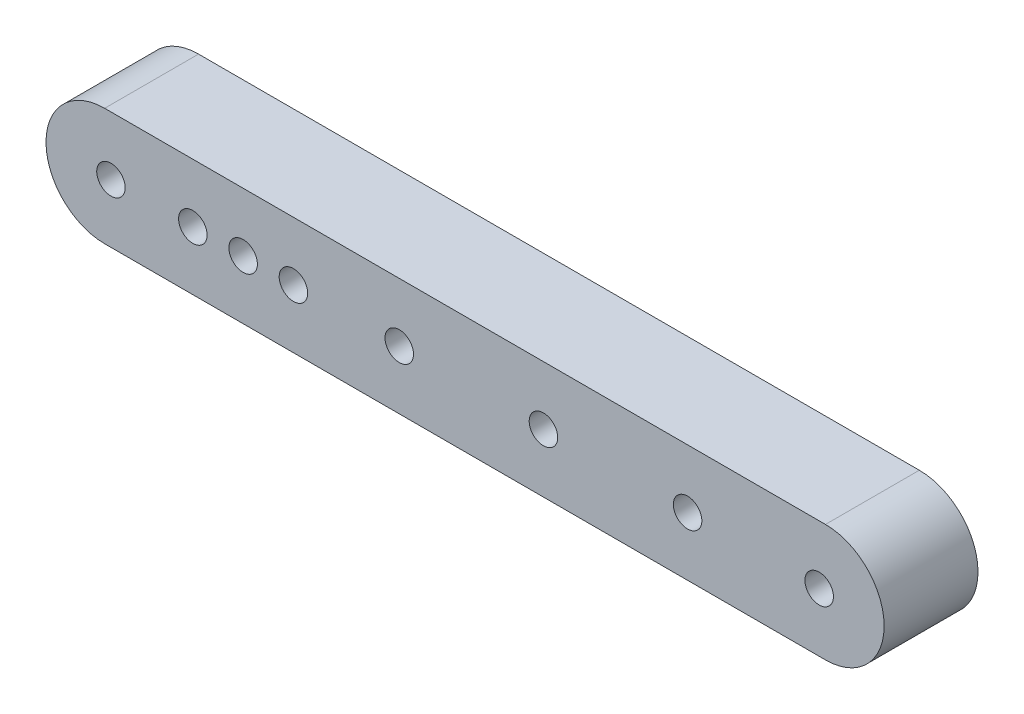
SolidWorks part; units mm, degrees
ref_plane "Front Plane" through (0, 0, 0) normal (0, 0, 1) x (1, 0, 0)
ref_plane "Top Plane" through (0, 0, 0) normal (0, 1, 0) x (1, 0, 0)
ref_plane "Right Plane" through (0, 0, 0) normal (1, 0, 0) x (0, 0, -1)
sketch "Sketch1" plane through (0, 0, 0) normal (0, 0, 1) x (1, 0, 0)
  line L0 (-33.3096, 0) -> (9.6904, 0) construction
  line L1 (-33.3096, 3.5) -> (9.6904, 3.5)
  line L2 (-33.3096, -3.5) -> (9.6904, -3.5)
  arc A0 (-33.3096, 3.5) -> (-33.3096, -3.5) centre (-33.3096, 0) ccw
  arc A1 (9.6904, -3.5) -> (9.6904, 3.5) centre (9.6904, 0) ccw
  point P3 (-11.8096, 0)
  point P8 (-36.8096, 0)
  point P9 (13.1904, 0)
  dimension "D1" = 50
  dimension "D2" = 7
extrude "Boss-Extrude1" add sketch "Sketch1" along normal blind 2.8 and the other way blind 2.8
scale "Echelle1" scale about centroid uniform scaling yes scale factor 2
sketch "Sketch2" plane through (0, 0, -5.6) normal (0, 0, 1) x (1, 0, 0)
  circle A3 centre (-38.2896, 0) radius 1.7
  circle A7 centre (-54.0596, 0) radius 1.7
  circle A29 centre (-19.6596, 0) radius 1.7
  circle A30 centre (-2.4596, 0) radius 1.7
  circle A31 centre (14.7404, 0) radius 1.7
  circle A33 centre (-44.2896, 0) radius 1.7
  circle A34 centre (-36.8596, 0) radius 1.7 [skipped]
  circle A35 centre (-32.2896, 0) radius 1.7
  arc A36 (-54.8096, 7) -> (-54.8096, -7) centre (-54.8096, 0) ccw construction
  circle A38 centre (31.9404, 0) radius 1.7 [skipped]
  circle A39 centre (30.4404, 0) radius 1.7
  arc A40 (31.1904, -7) -> (31.1904, 7) centre (31.1904, 0) ccw construction
  point P23 (-61.8096, 0)
  point P25 (38.1904, 0)
  dimension "D1" = 3.4
  dimension "D2" = 6
  dimension "D3" = 3.4
  dimension "D6" = 6
  dimension "D7" = 3.4
  dimension "D8" = 6
  dimension "D4" = 3.4
  dimension "D10" = 3.4
  dimension "D5" = 15.77
  dimension "D9" = 7.75
  dimension "D11" = 7.75
extrude "Cut-Extrude6" cut sketch "Sketch2" along normal up to surface (11.2 mm away) up to face at (-11.8096, 0, 5.6)
equation "\"ScrewSize\"= 2.9mm"
